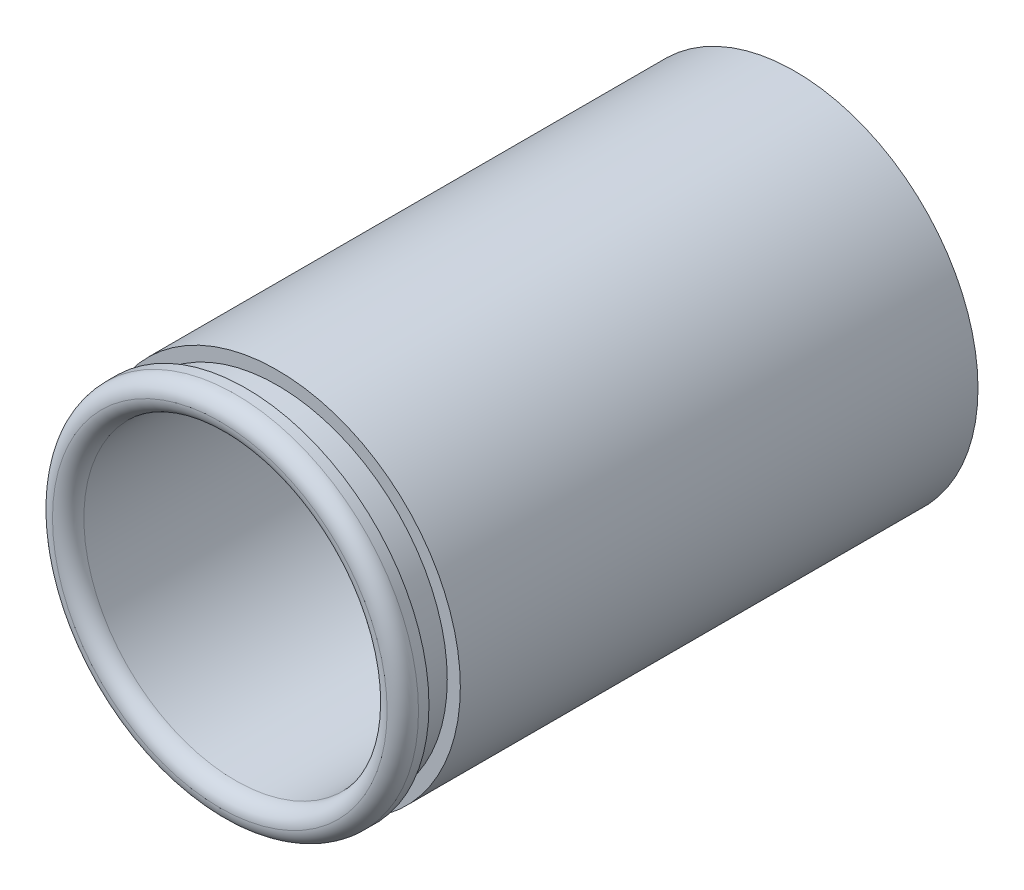
SolidWorks part; units mm, degrees
ref_plane "Plan1" through (0, 0, 0) normal (0, 0, 1) x (1, 0, 0)
ref_plane "Plan2" through (0, 0, 0) normal (0, 1, 0) x (1, 0, 0)
ref_plane "Plan3" through (0, 0, 0) normal (1, 0, 0) x (0, 0, -1)
sketch "Esquisse1" plane through (0, 0, 0) normal (0, 0, 1) x (1, 0, 0)
  circle A0 centre (0, 0) radius 2.9
  circle A1 centre (0, 0) radius 3.5
  dimension "D1" = 5.8
  dimension "D2" = 7
extrude "Base-Extrusion" add sketch "Esquisse1" along normal blind 11
sketch "Esquisse2" plane through (0, 0, 0) normal (1, 0, 0) x (0, 0, -1)
  line L1 (-10.5, 3.5) -> (-9.9, 3.5)
  line L2 (-10.5, 3.5) -> (-10.5, 3.25)
  line L3 (-10.5, 3.25) -> (-9.9, 3.25)
  line L4 (-9.9, 3.5) -> (-9.9, 3.25)
  line L5 (0, 3.5) -> (-11, 3.5) construction
  line L6 (-10, 0) -> (0, 0) construction
  line L7 (-11, 0) -> (0, 0) construction
  line L8 (-11, 3.5) -> (-11, -3.5) construction
  dimension "D1" = 0.6
  dimension "D2" = 0.25
  dimension "D3" = 0.5
revolve "Enlèvement de matière-Révolution1" cut sketch "Esquisse2" angle 360 about L6
fillet "Congé3" radius 0.3
